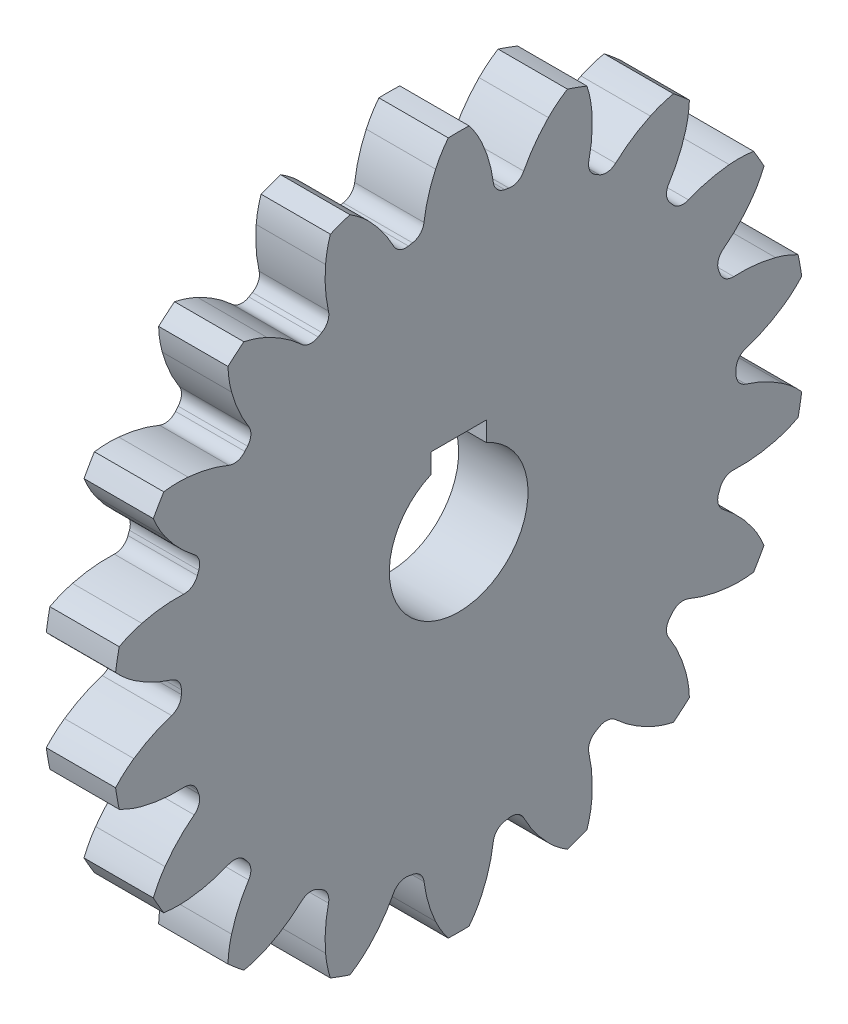
SolidWorks part; units mm, degrees
material "Cast Alloy Steel"
ref_plane "Front Plane" through (0, 0, 0) normal (0, 0, 1) x (1, 0, 0)
ref_plane "Top Plane" through (0, 0, 0) normal (0, 1, 0) x (1, 0, 0)
ref_plane "Right Plane" through (0, 0, 0) normal (1, 0, 0) x (0, 0, -1)
sketch "Sketch1" plane through (0, 0, 0) normal (1, 0, 0) x (0, 0, -1)
  circle A0 centre (0, 0) radius 45 construction
  circle A1 centre (0, 0) radius 50 construction
  circle A2 centre (0, 0) radius 40
  dimension "D1" = 90
  dimension "D2" = 100
  dimension "D3" = 80
extrude "Boss-Extrude1" add sketch "Sketch1" along normal blind 10
sketch "Sketch2" plane through (0, 0, 0) normal (1, 0, 0) x (0, 0, -1)
  line L0 (0, 0) -> (0, 75.7485) construction
  line L1 (-6.6512, 39.4431) -> (0, 0)
  line L2 (6.6512, 39.4431) -> (0, 0)
  arc A0 (-5, 41.1613) -> (-3.3303, 46.9826) centre (14.8381, 38.6214) cw
  arc A1 (-3.3303, 46.9826) -> (-1.5, 49.9775) centre (10.296, 40.7117) cw
  circle A2 centre (0, 0) radius 50 construction
  arc A3 (-1.5, 49.9775) -> (1.5, 49.9775) centre (0, 0) cw
  circle A4 centre (0, 0) radius 40 construction
  circle A5 centre (0, 0) radius 40 construction
  arc A6 (-5, 41.1613) -> (-6.6512, 39.4431) centre (-6.9838, 41.4153) cw
  arc A7 (5, 41.1613) -> (6.6512, 39.4431) centre (6.9838, 41.4153) ccw
  arc A8 (5, 41.1613) -> (3.3303, 46.9826) centre (-14.8381, 38.6214) ccw
  arc A9 (3.3303, 46.9826) -> (1.5, 49.9775) centre (-10.296, 40.7117) ccw
  point P9 (0, 50)
  dimension "D1" = 15
  dimension "D2" = 20
  dimension "D3" = 3
  dimension "D4" = 2
  dimension "D5" = 10
  dimension "D6" = 13.3025
extrude "Boss-Extrude2" add sketch "Sketch2" along normal blind 10
ref_axis "Axis1" through (-0.5, 0, 0) along (1, 0, 0)
pattern_circular "CirPattern1" count 18 over 360 about axis through (-0.5, 0, 0) along (1, 0, 0) of "Boss-Extrude2"
sketch "Sketch3" plane through (0, 0, 0) normal (1, 0, 0) x (0, 0, -1)
  line L0 (-4, 9.1652) -> (-4, 12)
  line L1 (-4, 12) -> (4, 12)
  line L2 (4, 12) -> (4, 9.1652)
  arc A0 (-4, 9.1652) -> (4, 9.1652) centre (0, 0) ccw
  point P5 (0, 12)
  dimension "D1" = 20
  dimension "D2" = 8
  dimension "D3" = 12
extrude "Cut-Extrude1" cut sketch "Sketch3" along normal through all
